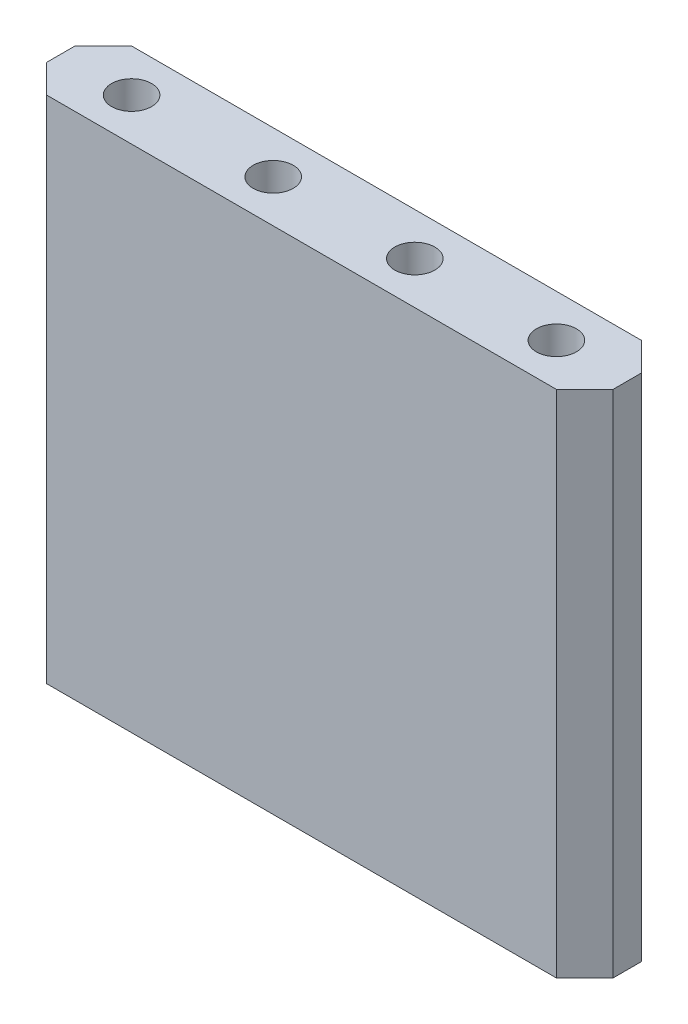
SolidWorks part; units mm, degrees
ref_plane "Спереди" through (0, 0, 0) normal (0, 0, 1) x (1, 0, 0)
ref_plane "Сверху" through (0, 0, 0) normal (0, 1, 0) x (1, 0, 0)
ref_plane "Справа" through (0, 0, 0) normal (1, 0, 0) x (0, 0, -1)
sketch "Эскиз1" plane through (0, 0, 0) normal (0, 1, 0) x (1, 0, 0)
  line L0 (-3.5, 0.25) -> (-3.5, -0.25)
  line L2 (-4, -0.25) -> (-4, 0.25)
  line L4 (4, -0.25) -> (4, 0.25)
  line L5 (-4, -0.25) -> (4, 0.25) construction
  line L6 (-4, 0.25) -> (4, -0.25) construction
  line L7 (-1.5, 0.25) -> (-1.5, -0.25)
  line L8 (-1, 0.25) -> (-1, -0.25)
  line L9 (1, 0.25) -> (1, -0.25)
  line L10 (3.5, 0.25) -> (3.5, -0.25)
  line L11 (1.5, 0.25) -> (1.5, -0.25)
  line L12 (-4, 0.25) -> (-3.5, 0.25)
  line L13 (-3.5, -0.25) -> (-4, -0.25)
  line L14 (-1.5, 0.25) -> (-1, 0.25)
  line L15 (-1, -0.25) -> (-1.5, -0.25)
  line L16 (1, -0.25) -> (1.5, -0.25)
  line L17 (1, 0.25) -> (1.5, 0.25)
  line L18 (3.5, -0.25) -> (4, -0.25)
  line L19 (3.5, 0.25) -> (4, 0.25)
  line L21 (-5, -0.75) -> (5, -0.75)
  line L22 (-5, -0.75) -> (-5, 0.75)
  line L23 (-5, 0.75) -> (5, 0.75)
  line L24 (5, -0.75) -> (5, 0.75)
  line L25 (-5, -0.75) -> (5, 0.75) construction
  line L26 (-5, 0.75) -> (5, -0.75) construction
  point P0 (0, 0)
  point P16 (0, 0)
  dimension "D1" = 0.5
  dimension "D2" = 2
  dimension "D3" = 0.5
  dimension "D4" = 2
  dimension "D5" = 0.5
  dimension "D6" = 2
  dimension "D7" = 8
  dimension "D8" = 0.5
extrude "Бобышка-Вытянуть1" add sketch "Эскиз1" along normal blind 7
sketch "Эскиз2" plane through (0, 7, 0) normal (0, 1, 0) x (1, 0, 0)
  line L0 (-4, 0) -> (-3.5, 0) construction
  line L1 (-5, -0.75) -> (5, -0.75)
  line L2 (-5, -0.75) -> (-5, 0.75)
  line L3 (-5, 0.75) -> (5, 0.75)
  line L4 (5, -0.75) -> (5, 0.75)
  line L5 (-5, -0.75) -> (5, 0.75) construction
  line L6 (-5, 0.75) -> (5, -0.75) construction
  line L7 (-4, 0.25) -> (-4, -0.25) construction
  line L8 (-3.5, -0.25) -> (-3.5, 0.25) construction
  line L9 (-1.5, 0) -> (-1, 0) construction
  line L10 (-1.5, 0.25) -> (-1.5, -0.25) construction
  line L11 (-1, -0.25) -> (-1, 0.25) construction
  line L12 (1, 0) -> (1.5, 0) construction
  line L13 (1, 0.25) -> (1, -0.25) construction
  line L14 (1.5, -0.25) -> (1.5, 0.25) construction
  line L15 (3.5, 0) -> (4, 0) construction
  line L16 (3.5, 0.25) -> (3.5, -0.25) construction
  line L17 (4, -0.25) -> (4, 0.25) construction
  circle A0 centre (-3.75, 0) radius 0.3536
  circle A1 centre (-1.25, 0) radius 0.3536
  circle A2 centre (1.25, 0) radius 0.3536
  circle A3 centre (3.75, 0) radius 0.3536
  point P0 (0, 0)
extrude "Бобышка-Вытянуть2" add sketch "Эскиз2" along normal blind 2
chamfer "Фаска1" distance 0.5 angle 45 4 edges at (-5, 4.5, 0.75) (-5, 4.5, -0.75) (5, 4.5, 0.75) (5, 4.5, -0.75)
